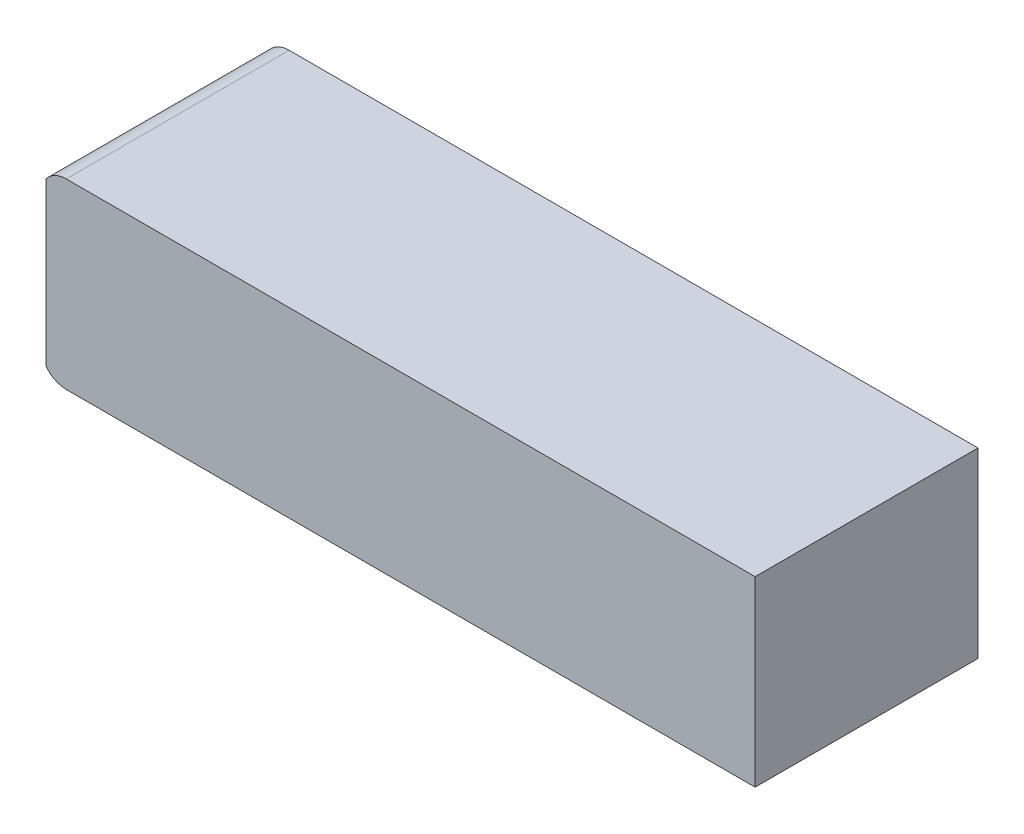
SolidWorks part; units mm, degrees
ref_plane "前视基准面" through (0, 0, 0) normal (0, 0, 1) x (1, 0, 0)
ref_plane "上视基准面" through (0, 0, 0) normal (0, 1, 0) x (1, 0, 0)
ref_plane "右视基准面" through (0, 0, 0) normal (1, 0, 0) x (0, 0, -1)
sketch "草图1" plane through (0, 0, 0) normal (0, 1, 0) x (1, 0, 0)
  line L1 (-70.5, -22) -> (70.5, -22)
  line L2 (-70.5, -22) -> (-70.5, 22)
  line L3 (-70.5, 22) -> (70.5, 22)
  line L4 (70.5, -22) -> (70.5, 22)
  line L5 (-70.5, -22) -> (70.5, 22) construction
  line L6 (-70.5, 22) -> (70.5, -22) construction
  point P0 (0, 0)
  dimension "D1" = 141
  dimension "D2" = 44
extrude "凸台-拉伸1" add sketch "草图1" along normal blind 36
fillet "圆角1" radius 5 2 edges at (-70.5, 0, 0) (-70.5, 36, 0)
chamfer "倒角1" distance 1 angle 45 1 edges at (-70.5, 18, 22) tangent propagation no
